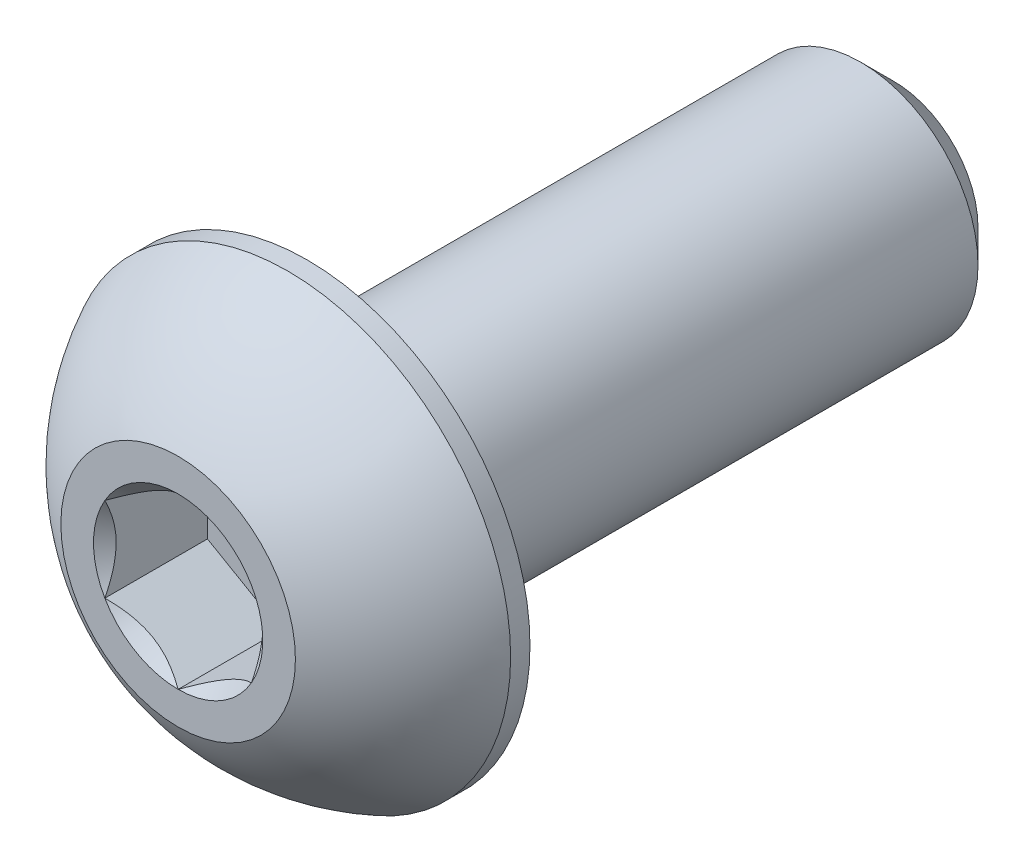
SolidWorks part; units mm, degrees
material "AISI 4340 Steel, normalized"
ref_plane "Front Plane" through (0, 0, 0) normal (0, 0, 1) x (1, 0, 0)
ref_plane "Top Plane" through (0, 0, 0) normal (0, 1, 0) x (1, 0, 0)
ref_plane "Right Plane" through (0, 0, 0) normal (1, 0, 0) x (0, 0, -1)
sketch "Sketch1" plane through (0, 0, 0) normal (1, 0, 0) x (0, 0, -1)
  line L0 (-6.1, 0) -> (6.1, 0) construction
  line L1 (-3.9, 3.8) -> (-3.9, -3.8) construction
  line L2 (6.1, 2) -> (6.1, -2) construction
  line L3 (6.0563, 2.0758) -> (6.4063, 1.4696) construction
  line L4 (6.4063, 1.4696) -> (6.7563, 2.0758) construction
  line L5 (6.7563, 2.0758) -> (6.0563, 2.0758) construction
  line L6 (6.1, 2) -> (6.7125, 2) construction
  line L7 (6.4063, 2.0758) -> (6.4063, 2) construction
  line L8 (6.4063, 2) -> (6.4063, 1.5453) construction
  line L9 (6.4063, 1.5453) -> (6.4063, 1.4696) construction
  line L10 (6.3625, 1.5453) -> (6.45, 1.5453)
  line L11 (6.0781, 2.0379) -> (6.7344, 2.0379)
  line L12 (6.45, 1.5453) -> (6.7344, 2.0379)
  line L13 (6.3625, 1.5453) -> (6.0781, 2.0379)
  line L14 (-6.1, 1.25) -> (-6.1, -1.25) construction
  line L15 (6.1, 2) -> (-3.9, 2) construction
  point P3 (-3.9, 0)
  point P6 (-4.35, 0)
  point P21 (6.4063, 2.0379)
  point P24 (-4.23, 3.8)
  point P25 (4.35, -2)
  point P26 (-6.1, 2)
  dimension "Head Height" = 2.2
  dimension "Length" = 10
  dimension "Head Dia" = 7.6
  dimension "Thread Dia" = 4
  dimension "Pitch" = 0.7
  dimension "D2" = 0.0875
  dimension "Drive Size" = 2.5
  dimension "D1" = 1.75
  dimension "D3" = 0.33
  dimension "D4" = 1.75
sketch "Sketch2" plane through (0, 0, 0) normal (1, 0, 0) x (0, 0, -1)
  line L0 (-6.1, 0) -> (6.1, 0)
  line L1 (6.1, 0) -> (6.1, 1.44)
  line L2 (6.1, 2) -> (6.1, -2) construction
  line L3 (6.1, 1.44) -> (5.54, 2)
  line L4 (5.54, 2) -> (-3.9, 2)
  line L5 (-3.9, 3.8) -> (-3.9, -3.8) construction
  line L6 (-3.9, 2) -> (-3.9, 3.8)
  line L7 (-3.9, 3.8) -> (-4.23, 3.8)
  line L8 (6.1, 2) -> (6.7125, 2) construction
  line L9 (-6.1, 0) -> (-6.1, 2)
  arc A0 (-6.1, 2) -> (-4.23, 3.8) centre (-2.3736, 0) cw
  dimension "D1" = 0.56
  dimension "D2" = 45
revolve "Revolve1" add sketch "Sketch2" angle 360 about L0
sketch "Sketch3" plane through (0, 0, 6.1) normal (0, 0, 1) x (1, 0, 0)
  line L1 (0, 1.4434) -> (-1.25, 0.7217)
  line L2 (-1.25, 0.7217) -> (-1.25, -0.7217)
  line L3 (-1.25, -0.7217) -> (0, -1.4434)
  line L4 (0, -1.4434) -> (1.25, -0.7217)
  line L5 (1.25, -0.7217) -> (1.25, 0.7217)
  line L6 (1.25, 0.7217) -> (0, 1.4434)
  circle A0 centre (0, 0) radius 1.25 construction
  dimension "D1" = 2.5
extrude "Cut-Extrude1" cut sketch "Sketch3" against normal up to vertex (1.75 mm away) up to point (0, 0, 4.35)
sketch "Sketch4" plane through (0, 0, 6.1) normal (0, 0, 1) x (1, 0, 0)
  circle A0 centre (0, 0) radius 1.4434
extrude "Cut-Extrude2" cut sketch "Sketch4" against normal blind 10 draft 45
equation "\"D2@Sketch1\" = \"Pitch@Sketch1\" / 8"
equation "\"D1@Sketch1\"=\"Drive Size@Sketch1\"*.7"
equation "\"D3@Sketch1\"=\"Head Height@Sketch1\"*.15"
equation "\"D1@Sketch2\"=\"Pitch@Sketch1\"*.8"
equation "\"D1@Sketch3\"=\"Drive Size@Sketch1\""
equation "\"D4@Sketch1\"=\"Pitch@Sketch1\"*2.5"
